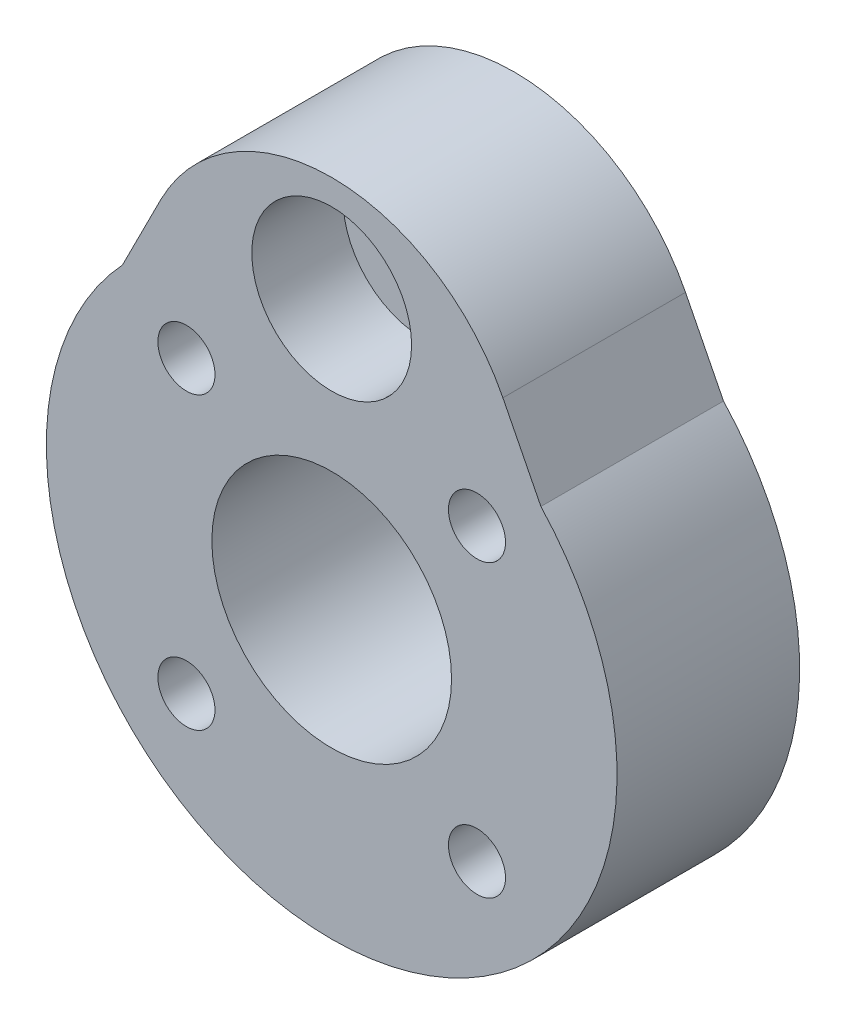
SolidWorks part; units mm, degrees
ref_plane "Front" through (0, 0, 0) normal (0, 0, 1) x (1, 0, 0)
ref_plane "Top" through (0, 0, 0) normal (0, 1, 0) x (1, 0, 0)
ref_plane "Right" through (0, 0, 0) normal (1, 0, 0) x (0, 0, -1)
sketch "Esquisse1" plane through (0, 0, 0) normal (0, 0, 1) x (1, 0, 0)
  circle A0 centre (0, 0) radius 12.5
  circle A1 centre (0, 0) radius 5.25
  dimension "D1" = 25
  dimension "D2" = 10.5
extrude "Boss.-Extru.1" add sketch "Esquisse1" along normal blind 8
sketch "Esquisse2" plane through (0, 0, 8) normal (0, 0, 1) x (1, 0, 0)
  line L0 (0, 0) -> (0, 8) construction
  line L1 (7.5, 11.7928) -> (-7.5, 11.7928) construction
  line L2 (0, 8) -> (0, 23.3526) construction
  line L3 (-7.5, 11.7928) -> (-9.1652, 8.5)
  line L4 (-9.1652, 8.5) -> (0, 8.5)
  line L5 (9.1652, 8.5) -> (0, 8.5)
  line L6 (7.5, 11.7928) -> (9.1652, 8.5)
  arc A0 (-7.5, 11.7928) -> (7.5, 11.7928) centre (0, 8) cw
  circle A1 centre (0, 0) radius 12.5 construction
  dimension "D1" = 8
  dimension "D2" = 15
  dimension "D3" = 8.5
extrude "Boss.-Extru.2" add sketch "Esquisse2" against normal up to surface (8 mm away) up to face at (12.5, 0, 0)
sketch "Esquisse3" plane through (0, 0, 8) normal (0, 0, 1) x (1, 0, 0)
  line L0 (0, 0) -> (-6.364, 6.364) construction
  line L1 (0, 0) -> (-4.1556, 0) construction
  circle A0 centre (-6.364, 6.364) radius 1.25
  circle A1 centre (6.364, 6.364) radius 1.25
  circle A2 centre (6.364, -6.364) radius 1.25
  circle A3 centre (-6.364, -6.364) radius 1.25
  point P13 (0, 0)
  dimension "D1" = 9
  dimension "D2" = 2.5
  dimension "D4" = 45
  dimension "D3" = 4
extrude "Enlèv. mat.-Extru.1" cut sketch "Esquisse3" against normal through all
sketch "Esquisse4" plane through (0, 0, 8) normal (0, 0, 1) x (1, 0, 0)
  line L0 (-7.5, 11.7928) -> (7.5, 11.7928) construction
  circle A0 centre (0, 11.7928) radius 2
  dimension "D1" = 4
extrude "Enlèv. mat.-Extru.2" cut sketch "Esquisse4" against normal through all
sketch "Esquisse5" plane through (0, 0, 8) normal (0, 0, 1) x (1, 0, 0)
  circle A0 centre (0, 11.7928) radius 3.5
  dimension "D1" = 7
extrude "Enlèv. mat.-Extru.3" cut sketch "Esquisse5" against normal blind 4
